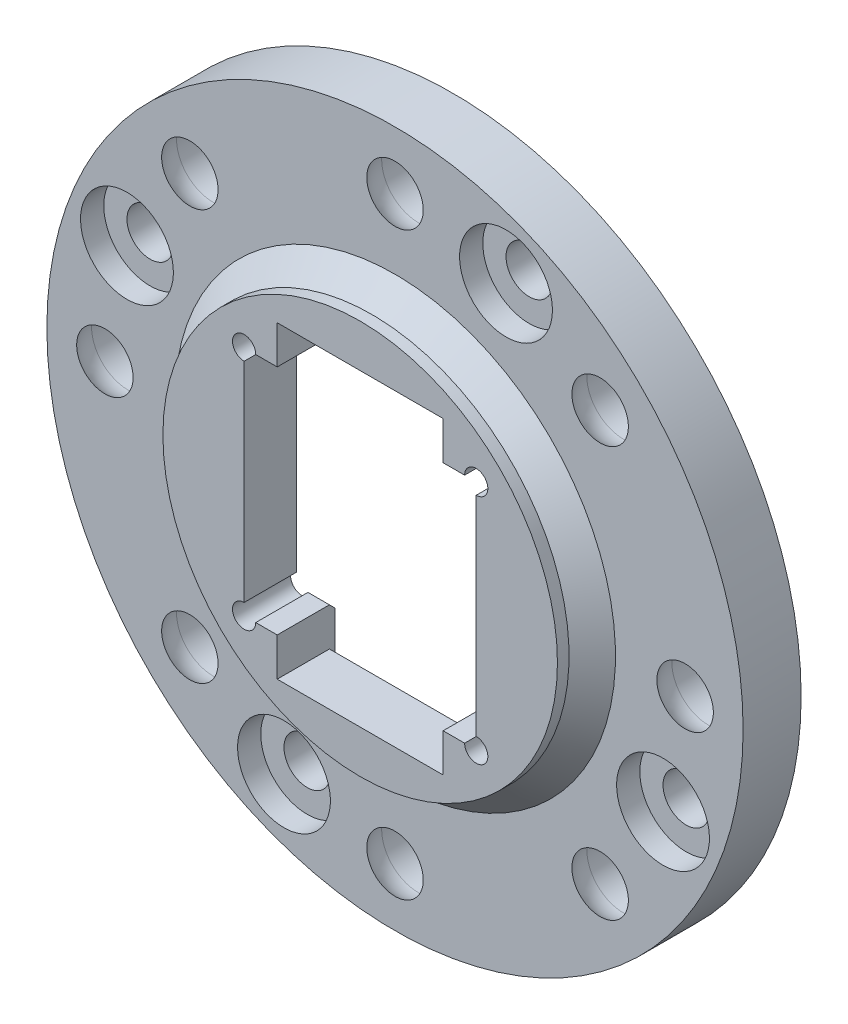
SolidWorks part; units mm, degrees
ref_plane "前视基准面" through (0, 0, 0) normal (0, 0, 1) x (1, 0, 0)
ref_plane "上视基准面" through (0, 0, 0) normal (0, 1, 0) x (1, 0, 0)
ref_plane "右视基准面" through (0, 0, 0) normal (1, 0, 0) x (0, 0, -1)
sketch "草图1" plane through (0, 0, 0) normal (0, 0, 1) x (1, 0, 0)
  line L0 (55, 0) -> (-55, 0) construction
  line L1 (-10, 10) -> (10, 10)
  line L2 (-10, 10) -> (-10, -10)
  line L3 (-10, -10) -> (10, -10)
  line L4 (10, 10) -> (10, -10)
  line L5 (-10, 10) -> (10, -10) construction
  line L6 (-10, -10) -> (10, 10) construction
  line L7 (-7.15, -10) -> (7.15, -10)
  line L8 (-7.15, -10) -> (-7.15, -13.3)
  line L9 (-7.15, -13.3) -> (7.15, -13.3)
  line L10 (7.15, -10) -> (7.15, -13.3)
  line L11 (-7.15, 13.3) -> (7.15, 13.3)
  line L12 (7.15, 10) -> (7.15, 13.3)
  line L13 (-7.15, 10) -> (7.15, 10)
  line L14 (-7.15, 10) -> (-7.15, 13.3)
  circle A0 centre (0, 0) radius 17
  circle A1 centre (10, 10) radius 1
  circle A2 centre (-10, 10) radius 1
  circle A3 centre (-10, -10) radius 1
  circle A4 centre (10, -10) radius 1
  point P15 (0, -13.3)
  dimension "D1" = 34
  dimension "D3" = 2
  dimension "D4" = 2
  dimension "D5" = 2
  dimension "D6" = 2
  dimension "D2" = 20
  dimension "D7" = 3.3
  dimension "D8" = 14.3
extrude "凸台-拉伸1" add sketch "草图1" along normal blind 5 contours A0 A4 L3 L10 L9 L8 A3 L2 A2 L1 L14 L11 L12 A1 L4 region at (-16.5192, 0, 0)
sketch "草图2" plane through (0, 0, 0) normal (0, 0, -1) x (-1, 0, 0)
  circle A0 centre (0, 0) radius 30
  circle A1 centre (0, 0) radius 17 construction
  circle A2 centre (0, 0) radius 17
  dimension "D1" = 60
extrude "凸台-拉伸2" add sketch "草图2" against normal blind 2
sketch "草图3" plane through (0, 0, 0) normal (0, 0, -1) x (-1, 0, 0)
  circle A0 centre (0, 0) radius 20
  circle A1 centre (0, 0) radius 30 construction
  circle A2 centre (0, 0) radius 30
  dimension "D1" = 40
extrude "凸台-拉伸3" add sketch "草图3" along normal blind 3
chamfer "倒角1" distance 2 angle 45 1 edges at (-17, 0, 2)
sketch "草图5" plane through (0, 0, 0) normal (1, 0, 0) x (0, 0, -1)
  line L0 (-998.8779, 25) -> (998.8779, 25) construction
  line L1 (3, 30) -> (-2, 30) construction
  line L2 (-2, 30) -> (-2, -30) construction
  line L3 (-3.15, 25) -> (3.15, 25)
  line L4 (0, 28.15) -> (3.15, 28.15)
  line L5 (3.15, 28.15) -> (3.15, 25)
  arc A0 (0, 28.15) -> (-3.15, 25) centre (0, 25) ccw
  point P4 (0, 25)
  dimension "D2" = 6.3
  dimension "D1" = 5
  dimension "D3" = 2
revolve "切除-旋转1" cut sketch "草图5" angle 360 about L0
ref_axis "基准轴1" through (0, 0, -3.4) along (0, 0, 1)
pattern_circular "阵列(圆周)1" count 8 over 360 about axis through (0, 0, -3.4) along (0, 0, 1) of "切除-旋转1"
sketch "草图6" plane through (0, 0, 2) normal (0, 0, 1) x (1, 0, 0)
  line L0 (0, -1000) -> (0, 49000) construction
  line L1 (0, 0) -> (9.5671, 23.097) construction
  circle A0 centre (9.5671, 23.097) radius 4
  dimension "D3" = 8
  dimension "D1" = 25
  dimension "D2" = 22.5
extrude "切除-拉伸1" cut sketch "草图6" against normal blind 2
sketch "草图7" plane through (0, 0, 0) normal (0, 0, 1) x (1, 0, 0)
  circle A0 centre (9.5671, 23.097) radius 2
  dimension "D1" = 4
extrude "切除-拉伸2" cut sketch "草图7" against normal through all
pattern_circular "阵列(圆周)2" count 4 over 360 about axis through (0, 0, -3.4) along (0, 0, 1) of "切除-拉伸2", "切除-拉伸1"
chamfer "倒角2" distance 0.5 angle 45 8 edges at (-10, 0, 0) (0, -13.3, 0) (10, 0, 0) (0, 13.3, 0) (-8.075, -10, 0) (8.075, -10, 0) (-8.075, 10, 0) (8.075, 10, 0)
chamfer "倒角3" distance 3 angle 45 1 edges at (-20, 0, 0)
sketch "草图8" plane through (0, 0, 0) normal (0, 0, -1) x (-1, 0, 0)
  line L0 (-9.134, 10.5) -> (-7.15, 10.5) construction
  line L1 (-13.5, 13.8) -> (13.5, 13.8)
  line L2 (-13.5, 13.8) -> (-13.5, 10.5)
  line L3 (-13.5, 10.5) -> (13.5, 10.5)
  line L4 (13.5, 13.8) -> (13.5, 10.5)
  line L5 (-13.5, 13.8) -> (13.5, 10.5) construction
  line L6 (-13.5, 10.5) -> (13.5, 13.8) construction
  line L7 (4.4, 0) -> (-4.4, 0) construction
  line L8 (-13.5, -10.5) -> (13.5, -10.5)
  line L9 (13.5, -13.8) -> (13.5, -10.5)
  line L10 (-13.5, -13.8) -> (13.5, -13.8)
  line L11 (-13.5, -13.8) -> (-13.5, -10.5)
  point P0 (0, 12.15)
  dimension "D1" = 3.3
  dimension "D2" = 27
extrude "切除-拉伸3" cut sketch "草图8" along normal through all
